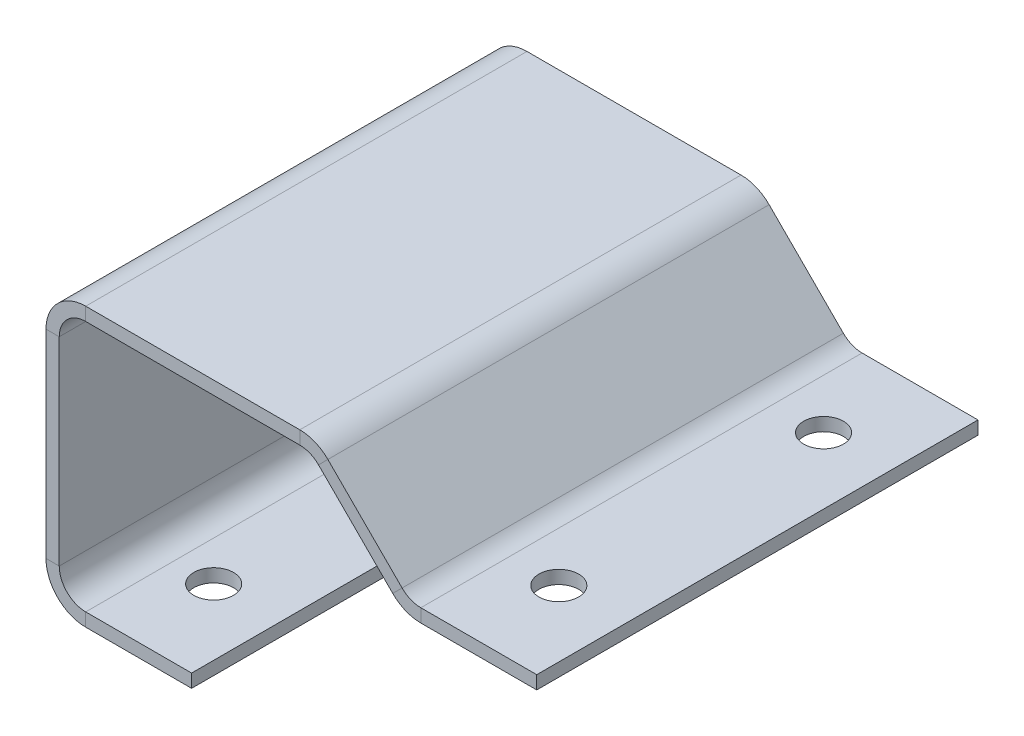
SolidWorks part; units mm, degrees
note: The reader was unsure of these and kept them because the rebuilt part matched: flange length of "Edge-Flange1", "Edge-Flange2", "Edge-Flange3", "Edge-Flange4".
ref_plane "Front Plane" through (0, 0, 0) normal (0, 0, 1) x (1, 0, 0)
ref_plane "Top Plane" through (0, 0, 0) normal (0, 1, 0) x (1, 0, 0)
ref_plane "Right Plane" through (0, 0, 0) normal (1, 0, 0) x (0, 0, -1)
sketch "Sketch1" plane through (0, 0, 0) normal (0, 1, 0) x (1, 0, 0)
  line L0 (0, 15) -> (0, -15) construction
  line L1 (-7.5, -25) -> (7.5, -25)
  line L2 (-7.5, -25) -> (-7.5, 25)
  line L3 (-7.5, 25) -> (7.5, 25)
  line L4 (7.5, -25) -> (7.5, 25)
  line L5 (-7.5, -25) -> (7.5, 25) construction
  line L6 (-7.5, 25) -> (7.5, -25) construction
  circle A0 centre (0, 15) radius 2.25
  circle A1 centre (0, -15) radius 2.25
  point P0 (0, 0)
  dimension "D4" = 4.5
  dimension "D1" = 15
  dimension "D2" = 50
  dimension "D3" = 30
base flange "Base-Flange1" sketch "Sketch1" thickness 1.5 reverse thickness direction yes parameters "D1"=3
edge flange "Edge-Flange1" sketch "Sketch9" flange angle 90 flange length 30 flange position material outside bend radius 3 thickness 1.5 relief rectangular parameters "D6"=10
sketch "Sketch9" plane through (-7.5, 1.5, 0) normal (-1, 0, 0) x (0, 0, 1)
  line L2 (-25, 0) -> (-25, 28.5)
  line L3 (-25, 28.5) -> (25, 28.5)
  line L4 (25, 28.5) -> (25, 0)
  line L7 (-25, 0) -> (25, 0) construction
  line L8 (-25, 0) -> (25, 0)
bend "EdgeBend1" bend radius 3 bend angle 90 parameters "D5"=1
edge flange "Edge-Flange2" sketch "Sketch12" flange angle 90 flange length 30 flange position material outside bend radius 3 thickness 1.5 relief rectangular parameters "D6"=10
sketch "Sketch12" plane through (-7.5, 30, 0) normal (0, 1, 0) x (0, 0, 1)
  line L2 (-25, 0) -> (-25, 28.5)
  line L3 (-25, 28.5) -> (25, 28.5)
  line L4 (25, 28.5) -> (25, 0)
  line L7 (25, 0) -> (-25, 0) construction
  line L8 (25, 0) -> (-25, 0)
bend "EdgeBend2" bend radius 3 bend angle 90 parameters "D5"=2
edge flange "Edge-Flange3" sketch "Sketch15" flange angle 135 flange length 15 flange position material outside bend radius 3 thickness 1.5 relief rectangular parameters "D6"=10
sketch "Sketch15" plane through (21, 30, 0) normal (0.7071, 0.7071, 0) x (0, 0, 1)
  line L0 (25, 0) -> (-25, 0) construction
  line L1 (25, 0) -> (-25, 0)
  line L2 (-25, 0) -> (-25, 14.3787)
  line L3 (-25, 14.3787) -> (25, 14.3787)
  line L4 (25, 14.3787) -> (25, 0)
bend "EdgeBend3" bend radius 3 bend angle 45 parameters "D5"=3
edge flange "Edge-Flange4" sketch "Sketch18" flange angle 135 flange length 15 flange position material outside bend radius 3 thickness 1.5 relief rectangular parameters "D6"=10
sketch "Sketch18" plane through (32.2279, 20.8934, 0) normal (0, -1, 0) x (0, 0, -1)
  line L2 (-25, 0) -> (-25, 14.3787)
  line L3 (-25, 14.3787) -> (25, 14.3787)
  line L4 (25, 14.3787) -> (25, 0)
  line L7 (-25, 0) -> (25, 0) construction
  line L8 (-25, 0) -> (25, 0)
bend "EdgeBend4" bend radius 3 bend angle 45 parameters "D5"=4
sketch "Sketch19" plane through (0, 20.8934, 0) normal (0, 1, 0) x (1, 0, 0)
  line L0 (39.1066, 15) -> (39.1066, -15) construction
  line L1 (46.6066, 25) -> (46.6066, -25) construction
  circle A0 centre (39.1066, 15) radius 2.25
  circle A1 centre (39.1066, -15) radius 2.25
  point P4 (39.1066, 0)
  dimension "D2" = 4.5
  dimension "D1" = 30
  dimension "D3" = 7.5
extrude "Cut-Extrude1" cut sketch "Sketch19" against normal through all
sketch "Bend-Lines1" [suppressed] plane through (0, 0, 0) normal (0, 1, 0) x (1, 0, 0)
sketch "Bounding-Box1" [suppressed] plane through (0, 0, 0) normal (0, 1, 0) x (1, 0, 0)
sheet metal parameters "Sheet-Metal2" thickness 1.5 parameters "D1"=3
flat pattern "Flat-Pattern2" [suppressed]
sketch "Bend-Lines2" plane through (0, 0, 0) normal (0, 1, 0) x (1, 0, 0)
sketch3d "Bounding-Box2" [suppressed]
  line L0 (-7.5, -25, 0) -> (-7.5, 25, 0) construction
  line L1 (7.5, -25, 0) -> (7.5, 25, 0) construction
  line L2 (-7.5, -25, 0) -> (7.5, -25, 0) construction
  line L3 (-7.5, 25, 0) -> (7.5, 25, 0) construction
sheet metal parameters "Sheet-Metal3" thickness 1.5 parameters "D1"=3
flat pattern "Flat-Pattern2"
sketch "Bend-Lines2" plane through (0, 0, 0) normal (0, -1, 0) x (-1, 0, 0)
  line L0 (5.9452, -25) -> (5.9452, 25) construction
  line L1 (5.9452, -25) -> (5.9452, 25) construction
sketch3d "Bounding-Box2" [suppressed]
  line L0 (39.3905, -25, 0) -> (39.3905, 25, 0) construction
  line L1 (-7.5, -25, 0) -> (-7.5, 25, 0) construction
  line L2 (39.3905, -25, 0) -> (-7.5, -25, 0) construction
  line L3 (39.3905, 25, 0) -> (-7.5, 25, 0) construction
bend of the flat pattern "Flatten-<EdgeBend1>1"
sheet metal parameters "Sheet-Metal4" thickness 1.5 parameters "D1"=3
flat pattern "Flat-Pattern2"
sketch "Bend-Lines2" plane through (0, 0, 0) normal (0, -1, 0) x (-1, 0, 0)
  line L0 (5.9452, -25) -> (5.9452, 25) construction
  line L1 (5.9452, -25) -> (5.9452, 25) construction
  line L2 (39.3357, -25) -> (39.3357, 25) construction
  line L3 (39.3357, -25) -> (39.3357, 25) construction
sketch3d "Bounding-Box2" [suppressed]
  line L0 (-7.5, 25, 0) -> (67.781, 25, 0) construction
  line L1 (-7.5, -25, 0) -> (67.781, -25, 0) construction
  line L2 (-7.5, 25, 0) -> (-7.5, -25, 0) construction
  line L3 (67.781, 25, 0) -> (67.781, -25, 0) construction
bend of the flat pattern "Flatten-<EdgeBend1>1"
bend of the flat pattern "Flatten-<EdgeBend2>1"
sheet metal parameters "Sheet-Metal5" thickness 1.5 parameters "D1"=3
flat pattern "Flat-Pattern2"
sketch "Bend-Lines2" plane through (0, 0, 0) normal (0, -1, 0) x (-1, 0, 0)
  line L0 (5.9452, -25) -> (5.9452, 25) construction
  line L1 (5.9452, -25) -> (5.9452, 25) construction
  line L2 (39.3357, -25) -> (39.3357, 25) construction
  line L3 (39.3357, -25) -> (39.3357, 25) construction
  line L4 (68.011, -25) -> (68.011, 25) construction
  line L5 (68.011, -25) -> (68.011, 25) construction
sketch3d "Bounding-Box2" [suppressed]
  line L0 (-7.5, 25, 0) -> (82.6196, 25, 0) construction
  line L1 (-7.5, -25, 0) -> (82.6196, -25, 0) construction
  line L2 (-7.5, 25, 0) -> (-7.5, -25, 0) construction
  line L3 (82.6196, 25, 0) -> (82.6196, -25, 0) construction
bend of the flat pattern "Flatten-<EdgeBend1>1"
bend of the flat pattern "Flatten-<EdgeBend2>1"
bend of the flat pattern "Flatten-<EdgeBend3>1"
sheet metal parameters "Sheet-Metal6" thickness 1.5 parameters "D1"=3
flat pattern "Flat-Pattern2"
sketch "Bend-Lines2" plane through (0, 0, 0) normal (0, -1, 0) x (-1, 0, 0)
  line L0 (5.9452, -25) -> (5.9452, 25) construction
  line L1 (5.9452, -25) -> (5.9452, 25) construction
  line L2 (39.3357, -25) -> (39.3357, 25) construction
  line L3 (39.3357, -25) -> (39.3357, 25) construction
  line L4 (68.011, -25) -> (68.011, 25) construction
  line L5 (68.011, -25) -> (68.011, 25) construction
  line L6 (82.8496, -25) -> (82.8496, 25) construction
  line L7 (82.8496, -25) -> (82.8496, 25) construction
sketch3d "Bounding-Box2" [suppressed]
  line L0 (-7.5, 25, 0) -> (97.4583, 25, 0) construction
  line L1 (-7.5, -25, 0) -> (97.4583, -25, 0) construction
  line L2 (-7.5, 25, 0) -> (-7.5, -25, 0) construction
  line L3 (97.4583, 25, 0) -> (97.4583, -25, 0) construction
bend of the flat pattern "Flatten-<EdgeBend1>1"
bend of the flat pattern "Flatten-<EdgeBend2>1"
bend of the flat pattern "Flatten-<EdgeBend3>1"
bend of the flat pattern "Flatten-<EdgeBend4>1"
sheet metal parameters "Sheet-Metal7" thickness 1.5 parameters "D1"=3
flat pattern "Flat-Pattern2"
sketch "Bend-Lines2" plane through (0, 0, 0) normal (0, -1, 0) x (-1, 0, 0)
  line L0 (7.4452, -25) -> (7.4452, 25) construction
  line L1 (7.4452, -25) -> (7.4452, 25) construction
  line L2 (35.8357, -25) -> (35.8357, 25) construction
  line L3 (35.8357, -25) -> (35.8357, 25) construction
  line L4 (64.511, -25) -> (64.511, 25) construction
  line L5 (64.511, -25) -> (64.511, 25) construction
  line L6 (79.3496, -25) -> (79.3496, 25) construction
  line L7 (79.3496, -25) -> (79.3496, 25) construction
sketch3d "Bounding-Box2" [suppressed]
  line L0 (-7.5, 25, 0) -> (93.9583, 25, 0) construction
  line L1 (-7.5, -25, 0) -> (93.9583, -25, 0) construction
  line L2 (-7.5, 25, 0) -> (-7.5, -25, 0) construction
  line L3 (93.9583, 25, 0) -> (93.9583, -25, 0) construction
bend of the flat pattern "Flatten-<EdgeBend1>1"
bend of the flat pattern "Flatten-<EdgeBend2>1"
bend of the flat pattern "Flatten-<EdgeBend3>1"
bend of the flat pattern "Flatten-<EdgeBend4>1"
